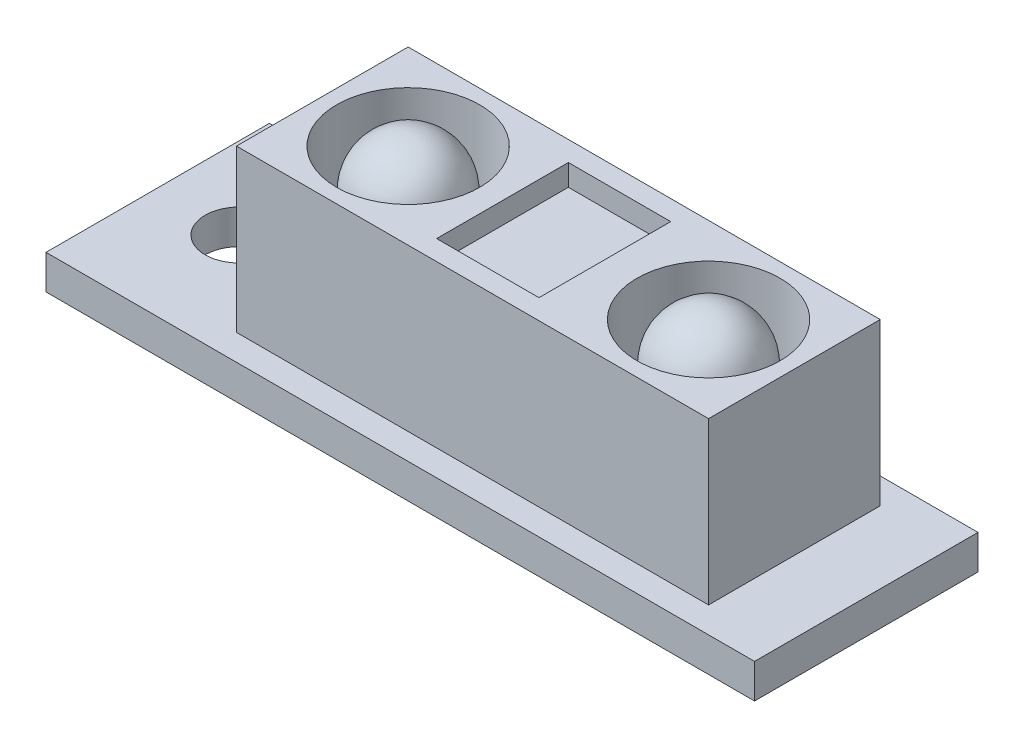
SolidWorks part; units mm, degrees
material "ABS"
ref_plane "Front Plane" through (0, 0, 0) normal (0, 0, 1) x (1, 0, 0)
ref_plane "Top Plane" through (0, 0, 0) normal (0, 1, 0) x (1, 0, 0)
ref_plane "Right Plane" through (0, 0, 0) normal (1, 0, 0) x (0, 0, -1)
sketch "Sketch1" plane through (0, 0, 0) normal (0, 1, 0) x (1, 0, 0)
  line L1 (-16.51, 5.207) -> (16.51, 5.207)
  line L2 (-16.51, 5.207) -> (-16.51, -5.207)
  line L3 (-16.51, -5.207) -> (16.51, -5.207)
  line L4 (16.51, 5.207) -> (16.51, -5.207)
  line L5 (-16.51, 5.207) -> (16.51, -5.207) construction
  line L6 (-16.51, -5.207) -> (16.51, 5.207) construction
  point P0 (0, 0)
  dimension "D1" = 10.414
  dimension "D2" = 33.02
extrude "Boss-Extrude1" add sketch "Sketch1" along normal blind 1.6
sketch "Sketch2" plane through (0, 1.6, 0) normal (0, 1, 0) x (1, 0, 0)
  line L0 (-14.1698, -0.4631) -> (-16.51, 0)
  line L1 (-16.51, 5.207) -> (-16.51, -5.207) construction
  line L2 (-16.51, 0) -> (16.51, 0) construction
  line L3 (16.51, -5.207) -> (16.51, 5.207) construction
  circle A0 centre (-12.7, 0) radius 1.6
  dimension "D2" = 3.2
  dimension "D1" = 29.21
extrude "Cut-Extrude1" cut sketch "Sketch2" against normal through all contours A0 L2 | L2 A0 region at (-12.7, 1.6, 0.6791) region at (-12.7, 1.6, -0.6791)
sketch "Sketch3" plane through (0, 1.6, 0) normal (0, 1, 0) x (1, 0, 0)
  line L0 (-16.51, 0) -> (16.51, 0) construction
  line L1 (-16.51, 5.207) -> (-16.51, -5.207) construction
  line L2 (16.51, -5.207) -> (16.51, 5.207) construction
  line L4 (13.16, 4) -> (-8.84, 4)
  line L5 (13.16, 4) -> (13.16, -4)
  line L6 (13.16, -4) -> (-8.84, -4)
  line L7 (-8.84, 4) -> (-8.84, -4)
  line L8 (13.16, 4) -> (-8.84, -4) construction
  line L9 (13.16, -4) -> (-8.84, 4) construction
  point P6 (2.16, 0)
  dimension "D1" = 3.35
  dimension "D2" = 22
  dimension "D3" = 8
extrude "Boss-Extrude2" add sketch "Sketch3" along normal blind 7.52
ref_plane "Plane1" through (-8.84, 9.12, 4) normal (1, 0, 0) x (0, 0, -1)
sketch "Sketch5" plane through (0, 9.12, 0) normal (0, 1, 0) x (1, 0, 0)
  line L0 (2.16, -4) -> (2.16, 4) construction
  line L1 (-8.84, -4) -> (13.16, -4) construction
  line L2 (13.16, 4) -> (-8.84, 4) construction
  line L3 (-8.84, 0) -> (13.16, 0) construction
  line L4 (-8.84, 4) -> (-8.84, -4) construction
  line L5 (13.16, -4) -> (13.16, 4) construction
  circle A0 centre (-4.84, 0) radius 3.335
  circle A1 centre (9.16, 0) radius 3.335
  dimension "D1" = 6.67
  dimension "D2" = 6.67
  dimension "D3" = 4
extrude "Cut-Extrude2" cut sketch "Sketch5" against normal blind 5
sketch "Sketch6" plane through (0, 4.12, 0) normal (0, 1, 0) x (1, 0, 0)
  line L0 (-4.84, 3.335) -> (-4.84, -3.335) construction
  line L1 (-8.1702, 0.1787) -> (-1.505, 0) construction
  circle A0 centre (-4.84, 0) radius 3.335 construction
  circle A1 centre (-4.84, 0) radius 2.335
  dimension "D1" = 1
extrude "Boss-Extrude3" add sketch "Sketch6" along normal blind 3
dome "Dome1" faces to dome 1 distance 2.54 reverse direction no elliptical dome no face at (-4.84, 7.12, 2.335) parameters "D1"=2.54
ref_plane "Plane2" through (2.16, 0, 0) normal (1, 0, 0) x (0, 0, -1)
mirror "Mirror1" about plane through (2.16, 0, 0) normal (1, 0, 0) of "Boss-Extrude3", "Dome1"
sketch "Sketch7" plane through (0, 9.12, 0) normal (0, 1, 0) x (1, 0, 0)
  line L0 (13.16, 0) -> (-8.84, 0) construction
  line L1 (13.16, -4) -> (13.16, 4) construction
  line L2 (-8.84, 4) -> (-8.84, -4) construction
  line L3 (2.16, -4) -> (2.16, 4) construction
  line L4 (-8.84, -4) -> (13.16, -4) construction
  line L5 (13.16, 4) -> (-8.84, 4) construction
  line L8 (4.3272, -3.07) -> (-0.4428, -3.07)
  line L9 (4.3272, -3.07) -> (4.3272, 3.07)
  line L10 (4.3272, 3.07) -> (-0.4428, 3.07)
  line L11 (-0.4428, -3.07) -> (-0.4428, 3.07)
  line L12 (4.3272, -3.07) -> (-0.4428, 3.07) construction
  line L13 (4.3272, 3.07) -> (-0.4428, -3.07) construction
  point P12 (1.9422, 0)
  dimension "D1" = 4.77
  dimension "D2" = 6.14
extrude "Cut-Extrude3" cut sketch "Sketch7" against normal blind 1
